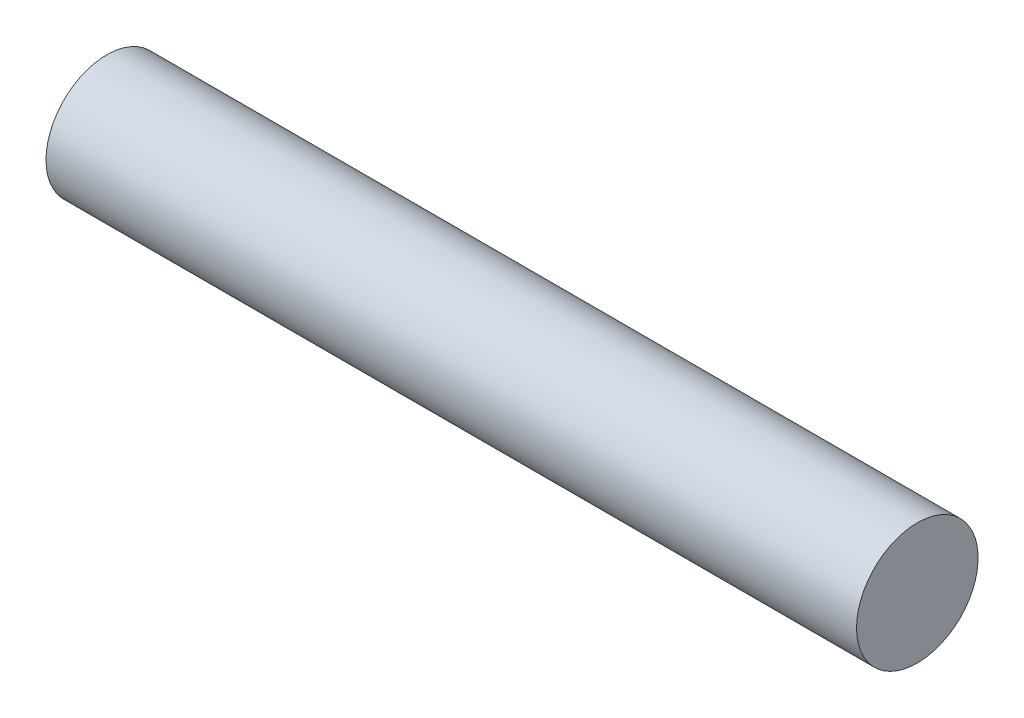
SolidWorks part; units mm, degrees
ref_plane "Front Plane" through (0, 0, 0) normal (0, 0, 1) x (1, 0, 0)
ref_plane "Top Plane" through (0, 0, 0) normal (0, 1, 0) x (1, 0, 0)
ref_plane "Right Plane" through (0, 0, 0) normal (1, 0, 0) x (0, 0, -1)
sketch "Sketch1" plane through (0, 0, 0) normal (0, 1, 0) x (1, 0, 0)
  line L0 (0, 0) -> (152.4, 0)
  line L5 (0, 0) -> (-38.1, 0)
  line L6 (152.4, 0) -> (190.5, 0)
  line L7 (-38.1, 0) -> (-38.1, -34.29)
  line L8 (-38.1, -34.29) -> (190.5, -34.29)
  line L9 (190.5, -34.29) -> (190.5, 0)
  line L10 (39.37, 0) -> (0, 0)
  line L11 (-38.1, -17.145) -> (190.5, -17.145) construction
  dimension "D4" = 152.4
  dimension "D5" = 38.1
  dimension "D6" = 38.1
  dimension "D7" = 34.29
  dimension "D8" = 39.37
revolve "Revolve2" add sketch "Sketch1" angle 360 about L11 region at (76.2, 0, 25.7175)
